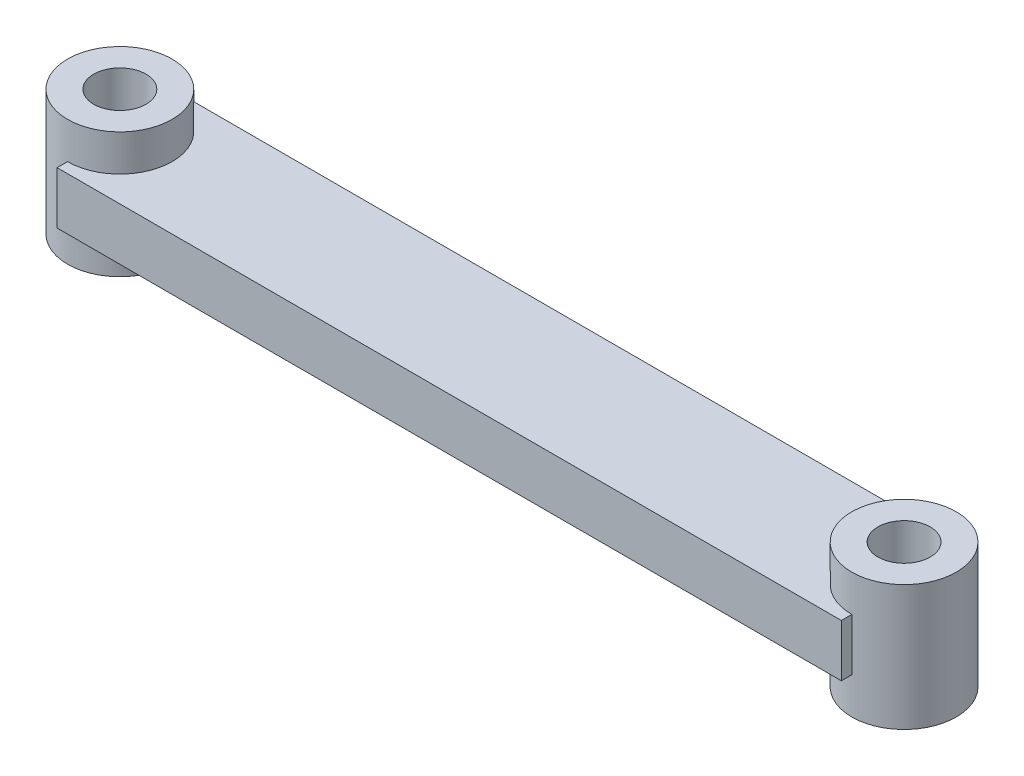
SolidWorks part; units mm, degrees
ref_plane "前视基准面" through (0, 0, 0) normal (0, 0, 1) x (1, 0, 0)
ref_plane "上视基准面" through (0, 0, 0) normal (0, 1, 0) x (1, 0, 0)
ref_plane "右视基准面" through (0, 0, 0) normal (1, 0, 0) x (0, 0, -1)
other "Configuration Table"
sketch "Sketch1" plane through (0, 0, 0) normal (1, 0, 0) x (0, 0, -1)
  line L1 (-24, -10) -> (24, -10)
  line L2 (-24, -10) -> (-24, 10)
  line L3 (-24, 10) -> (24, 10)
  line L4 (24, -10) -> (24, 10)
  line L5 (-24, -10) -> (24, 10) construction
  line L6 (-24, 10) -> (24, -10) construction
  point P0 (0, 0)
extrude "Boss-Extrude1" add sketch "Sketch1" along normal blind 300
sketch "Sketch2" plane through (0, 0, 0) normal (0, 1, 0) x (1, 0, 0)
  circle A0 centre (0, 0) radius 20
extrude "Boss-Extrude2" add sketch "Sketch2" along normal blind 24 and the other way blind 24
sketch "Sketch3" plane through (0, 0, 0) normal (0, 1, 0) x (1, 0, 0)
  line L0 (300, 24) -> (300, -24) construction
  circle A0 centre (300, 0) radius 20
extrude "Boss-Extrude3" add sketch "Sketch3" along normal blind 24 and the other way blind 24
sketch "Sketch4" plane through (0, 0, 0) normal (0, 1, 0) x (1, 0, 0)
  circle A0 centre (0, 0) radius 10
extrude "Cut-Extrude1" cut sketch "Sketch4" along normal blind 50 and the other way blind 50
sketch "Sketch5" plane through (0, 0, 0) normal (0, 1, 0) x (1, 0, 0)
  circle A0 centre (300, 0) radius 10
extrude "Cut-Extrude2" cut sketch "Sketch5" along normal blind 50 and the other way blind 50
sketch3d "3DSketch1"
  line L0 (0, -100, 0) -> (0, 100, 0) construction
ref_axis "start_hinge_axis_y" through (0, -100, 0) along (0, 1, 0)
sketch3d "3DSketch2"
  line L0 (300, -100, 0) -> (300, 100, 0) construction
ref_axis "end_hinge_axis_y" through (300, -100, 0) along (0, 1, 0)
sketch3d "3DSketch3"
  line L0 (0, 0, 0) -> (300, 0, 0) construction
ref_axis "longitudinal_axis_x" through (0, 0, 0) along (1, 0, 0)
ref_plane "ref_plane_start_face" through (0, 0, 0) normal (1, 0, 0) x (0, 0, -1)
ref_plane "ref_plane_end_face" through (300, 0, 0) normal (1, 0, 0) x (0, 0, -1)
ref_plane "ref_plane_side_y_plus" through (0, 24, 0) normal (0, 1, 0) x (1, 0, 0)
ref_plane "ref_plane_side_y_minus" through (0, -24, 0) normal (0, 1, 0) x (1, 0, 0)
